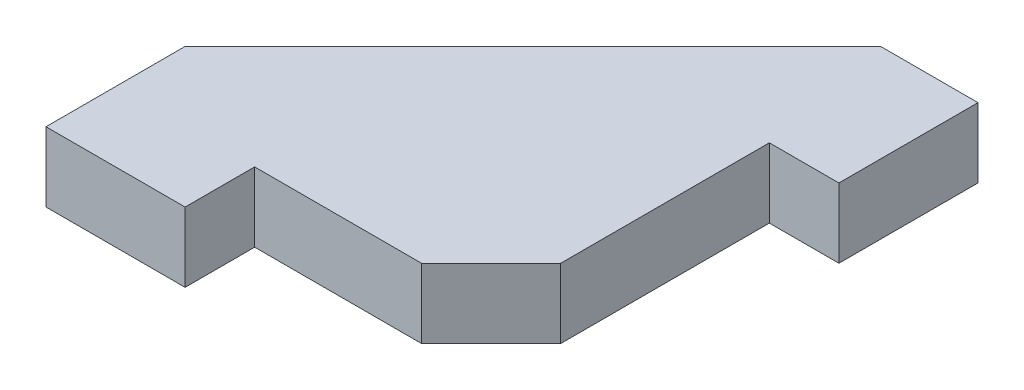
SolidWorks part; units mm, degrees
ref_plane "Front Plane" through (0, 0, 0) normal (0, 0, 1) x (1, 0, 0)
ref_plane "Top Plane" through (0, 0, 0) normal (0, 1, 0) x (1, 0, 0)
ref_plane "Right Plane" through (0, 0, 0) normal (1, 0, 0) x (0, 0, -1)
sketch "Sketch1" plane through (0, 0, 0) normal (0, 1, 0) x (1, 0, 0)
  line L0 (0, 0) -> (0, 10)
  line L1 (0, 10) -> (25, 35)
  line L2 (25, 35) -> (32, 35)
  line L3 (32, 35) -> (32, 25)
  line L4 (32, 25) -> (27, 25)
  line L5 (27, 25) -> (27, 10)
  line L6 (27, 10) -> (22, 5)
  line L7 (22, 5) -> (10, 5)
  line L8 (10, 5) -> (10, 0)
  line L9 (10, 0) -> (0, 0)
  dimension "D1" = 10
  dimension "D2" = 5
  dimension "D3" = 27
  dimension "D4" = 30
  dimension "D5" = 45
  dimension "D6" = 5
  dimension "D7" = 5
extrude "Boss-Extrude1" add sketch "Sketch1" along normal blind 5
